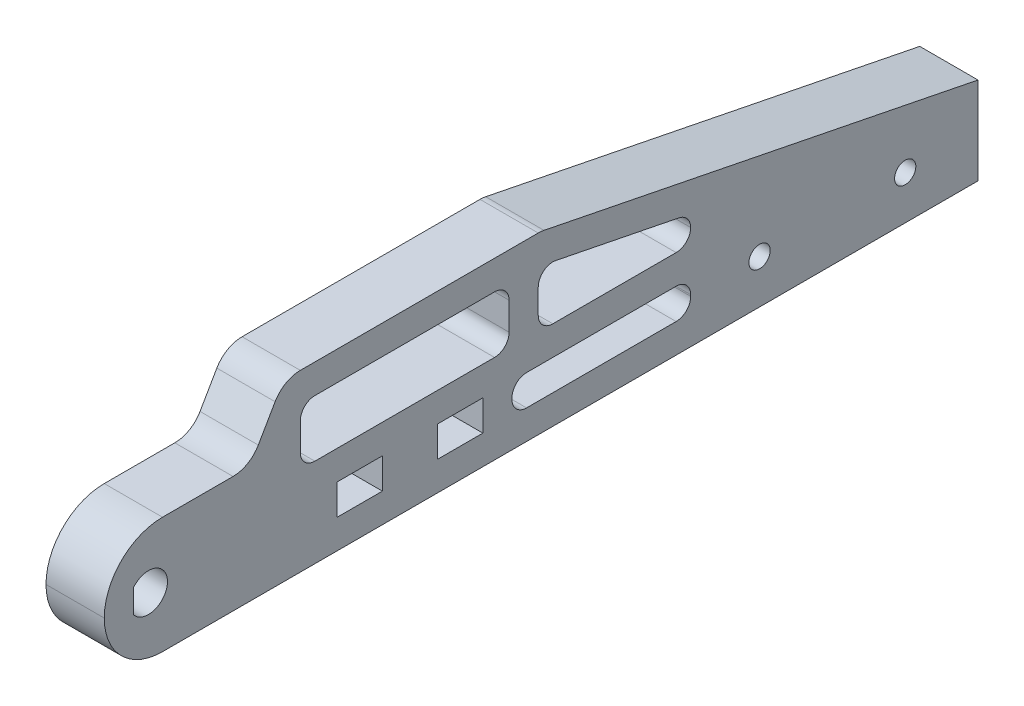
SolidWorks part; units mm, degrees
ref_plane "Front Plane" through (0, 0, 0) normal (0, 0, 1) x (1, 0, 0)
ref_plane "Top Plane" through (0, 0, 0) normal (0, 1, 0) x (1, 0, 0)
ref_plane "Right Plane" through (0, 0, 0) normal (1, 0, 0) x (0, 0, -1)
ref_plane "Plane1" through (0, 0, 0) normal (1, 0, 0) x (0, 0, -1)
sketch "Sketch1" plane through (0, 0, 0) normal (1, 0, 0) x (0, 0, -1)
  line L0 (0, 0) -> (150, 0)
  line L1 (150, 0) -> (150, 15)
  line L3 (150, 15) -> (75, 30)
  line L7 (25, 20) -> (30.7735, 30)
  line L8 (30.7735, 30) -> (75, 30)
  line L9 (0, 0) -> (0, 20)
  line L10 (0, 20) -> (25, 20)
  dimension "D1" = 150
  dimension "D2" = 15
  dimension "D3" = 75
  dimension "D5" = 25
  dimension "D6" = 20
  dimension "D7" = 10
  dimension "D8" = 120
extrude "Boss-Extrude1" add sketch "Sketch1" against normal blind 10
sketch "Sketch2" plane through (0, 0, 0) normal (1, 0, 0) x (0, 0, -1)
  line L20 (5, 11.9945) -> (5, 8.0055)
  line L23 (10.85, 19.5521) -> (10.85, 10.3168) construction
  line L26 (0, 20) -> (0, 0) construction
  arc A0 (5, 8.0055) -> (5, 11.9945) centre (7.585, 10) ccw
  point P0 (0, 10)
  dimension "D12" = 6.53
  dimension "D3" = 5
  dimension "D24" = 5.85
extrude "Cut-Extrude2" cut sketch "Sketch2" against normal through all
fillet "Fillet1" radius 10 2 edges at (-5, 0, 0) (-5, 20, 0)
fillet "Fillet2" radius 5 2 edges at (-5, 30, -75) (-5, 30, -30.7735)
sketch "Sketch5" plane through (0, 0, 0) normal (1, 0, 0) x (0, 0, -1)
  line L1 (135, 5) -> (140, 5)
  line L2 (135, 5) -> (135, 10)
  line L3 (135, 10) -> (140, 10)
  line L4 (140, 5) -> (140, 10)
  line L5 (135, 5) -> (140, 10) construction
  line L6 (135, 10) -> (140, 5) construction
  line L7 (110, 5) -> (115, 5)
  line L8 (110, 5) -> (110, 10)
  line L9 (110, 10) -> (115, 10)
  line L10 (115, 5) -> (115, 10)
  line L11 (110, 5) -> (115, 10) construction
  line L12 (110, 10) -> (115, 5) construction
  line L13 (150, 0) -> (150, 15) construction
  point P0 (137.5, 7.5)
  point P5 (112.5, 7.5)
  point P12 (150, 7.5)
  point P13 (140, 7.5)
  dimension "D1" = 5
  dimension "D2" = 5
  dimension "D3" = 10
  dimension "D4" = 20
  dimension "D5" = 5
  dimension "D6" = 5
extrude "Cut-Extrude5" [suppressed] cut sketch "Sketch5" against normal through all both and the other way through all
sketch "Sketch3" plane through (0, 0, 0) normal (1, 0, 0) x (0, 0, -1)
  line L6 (57.25, 5) -> (65, 5)
  line L11 (57.25, 5) -> (57.25, 10.25)
  line L12 (57.25, 10.25) -> (65, 10.25)
  line L17 (65, 5) -> (65, 10.25)
  line L19 (40, 10.25) -> (47.75, 10.25)
  line L20 (40, 10.25) -> (40, 5)
  line L21 (40, 5) -> (47.75, 5)
  line L22 (47.75, 10.25) -> (47.75, 5)
  line L23 (40, 10.25) -> (47.75, 5) construction
  line L24 (40, 5) -> (47.75, 10.25) construction
  line L29 (57.25, 5) -> (65, 10.25) construction
  line L30 (57.25, 10.25) -> (65, 5) construction
  line L48 (10, 0) -> (150, 0) construction
  point P0 (61.125, 7.625)
  point P15 (43.875, 7.625)
  dimension "D2" = 40
  dimension "D3" = 5.25
  dimension "D4" = 7.75
  dimension "D5" = 9.5
  dimension "D11" = 7.75
  dimension "D12" = 5.25
  dimension "D18" = 5
extrude "Cut-Extrude3" cut sketch "Sketch3" against normal through all both and the other way through all
sketch "Sketch6" plane through (0, 0, 0) normal (1, 0, 0) x (0, 0, -1)
  line L2 (150, 0) -> (150, 15) construction
  circle A0 centre (112.5, 7.5) radius 1.825
  circle A1 centre (137.5, 7.5) radius 1.825
  point P7 (150, 7.5)
  dimension "D1" = 3.65
  dimension "D2" = 3.65
  dimension "D3" = 12.5
  dimension "D4" = 25
extrude "Cut-Extrude6" cut sketch "Sketch6" against normal through all both and the other way through all
fillet "Fillet3" radius 5 1 edges at (-5, 20, -25)
sketch "Sketch7" plane through (0, 0, 0) normal (1, 0, 0) x (0, 0, -1)
  line L2 (69.5049, 25) -> (33.6603, 25)
  line L3 (33.6603, 25) -> (33.6603, 15.25)
  line L4 (70, 10.25) -> (100.675, 10.25)
  line L5 (100.675, 10.25) -> (100.675, 5)
  line L6 (100.675, 5) -> (70, 5)
  line L7 (70, 5) -> (70, 10.25)
  line L8 (10, 0) -> (150, 0) construction
  line L9 (65, 10.25) -> (65, 5) construction
  line L10 (100.675, 15.25) -> (100.675, 19.766)
  line L11 (74.5049, 30) -> (33.6603, 30) construction
  line L12 (100.675, 19.766) -> (74.5049, 25)
  line L13 (150, 15) -> (75.4855, 29.9029) construction
  line L14 (57.25, 10.25) -> (65, 10.25) construction
  line L15 (33.6603, 15.25) -> (69.5049, 15.25)
  line L16 (69.5049, 15.25) -> (69.5049, 25)
  line L17 (74.5049, 25) -> (74.5049, 15.25)
  line L18 (74.5049, 15.25) -> (100.675, 15.25)
  circle A0 centre (112.5, 7.5) radius 1.825 construction
  point P10 (100.675, 7.625)
  dimension "D1" = 5
  dimension "D2" = 5
  dimension "D3" = 11.825
  dimension "D4" = 5
  dimension "D5" = 5
  dimension "D6" = 5
  dimension "D7" = 5
extrude "Cut-Extrude7" cut sketch "Sketch7" against normal through all both and the other way through all
fillet "Fillet4" radius 2.5 12 edges at (-5, 5, -100.675) (-5, 10.25, -100.675) (-5, 10.25, -70) (-5, 5, -70) (-5, 15.25, -33.6603) (-5, 15.25, -69.5049) (-5, 25, -69.5049) (-5, 25, -33.6603) (-5, 15.25, -74.5049) (-5, 15.25, -100.675) (-5, 19.766, -100.675) (-5, 25, -74.5049)
